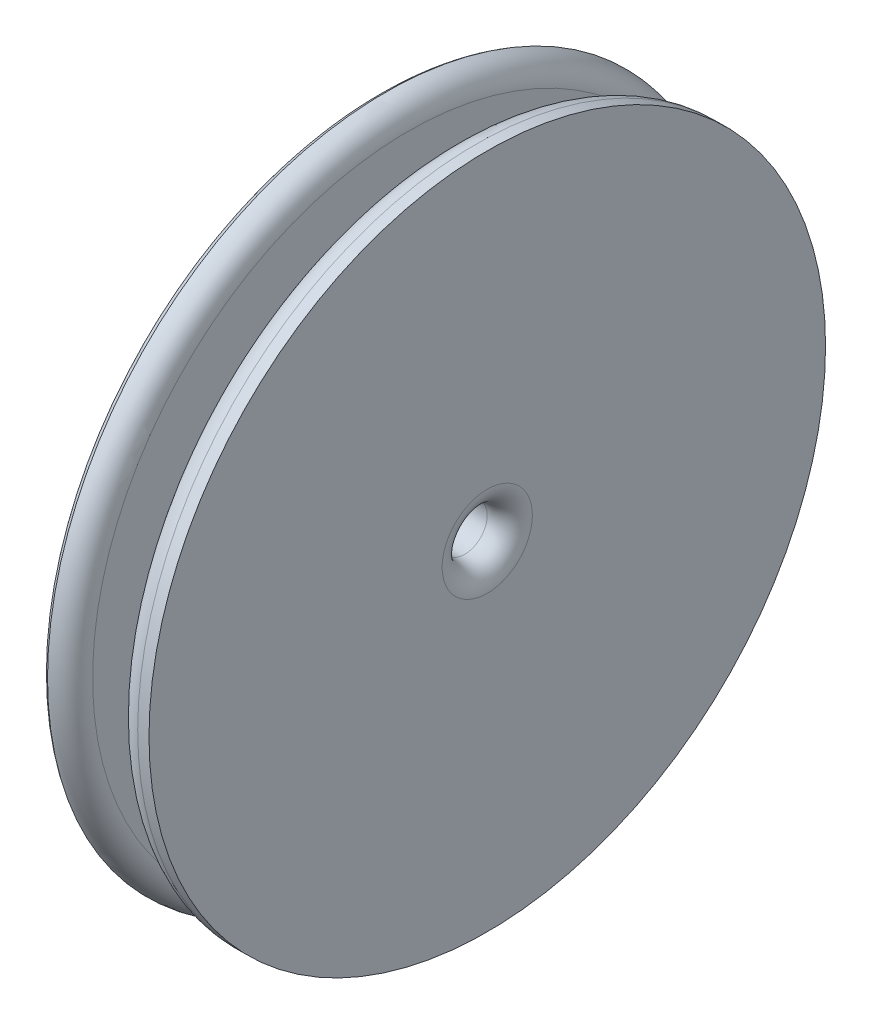
SolidWorks part; units mm, degrees
ref_plane "Front Plane" through (0, 0, 0) normal (0, 0, 1) x (1, 0, 0)
ref_plane "Top Plane" through (0, 0, 0) normal (0, 1, 0) x (1, 0, 0)
ref_plane "Right Plane" through (0, 0, 0) normal (1, 0, 0) x (0, 0, -1)
sketch "Sketch1" plane through (0, 0, 0) normal (0, 1, 0) x (1, 0, 0)
  line L0 (0, 0) -> (0, 24.6857)
  line L1 (0, 24.6857) -> (3, 24.6857)
  line L2 (3, 24.6857) -> (3, 0)
  line L3 (3, 0) -> (7, 0)
  line L4 (7, 0) -> (7, 24.6857)
  line L5 (7, 24.6857) -> (10, 24.6857)
  line L6 (10, 24.6857) -> (10, -5.3143)
  line L7 (10, -5.3143) -> (0, -5.3143)
  line L8 (0, -5.3143) -> (0, 0)
  point P7 (0, 0)
  point P11 (0, 0)
  dimension "D1" = 4
  dimension "D2" = 10
  dimension "D3" = 30
revolve "Revolve1" add sketch "Sketch1" angle 360 about L7
sketch "Sketch2" plane through (10, 0, 0) normal (1, 0, 0) x (0, 0, -1)
  circle A0 centre (-5.3143, 0) radius 2
  circle A1 centre (-5.3143, 0) radius 30 construction
  dimension "D1" = 4
extrude "Cut-Extrude1" cut sketch "Sketch2" against normal blind 10
fillet "Fillet1" radius 2 3 edges at (3, 0, -24.6857) (7, 0, 0) (3, 0, 0)
fillet "Fillet2" radius 2 2 edges at (7, 0, -24.6857) (10, 0, 3.3143)
fillet "Fillet3" radius 2 2 edges at (0, 0, -24.6857) (0, 0, 3.3143)
